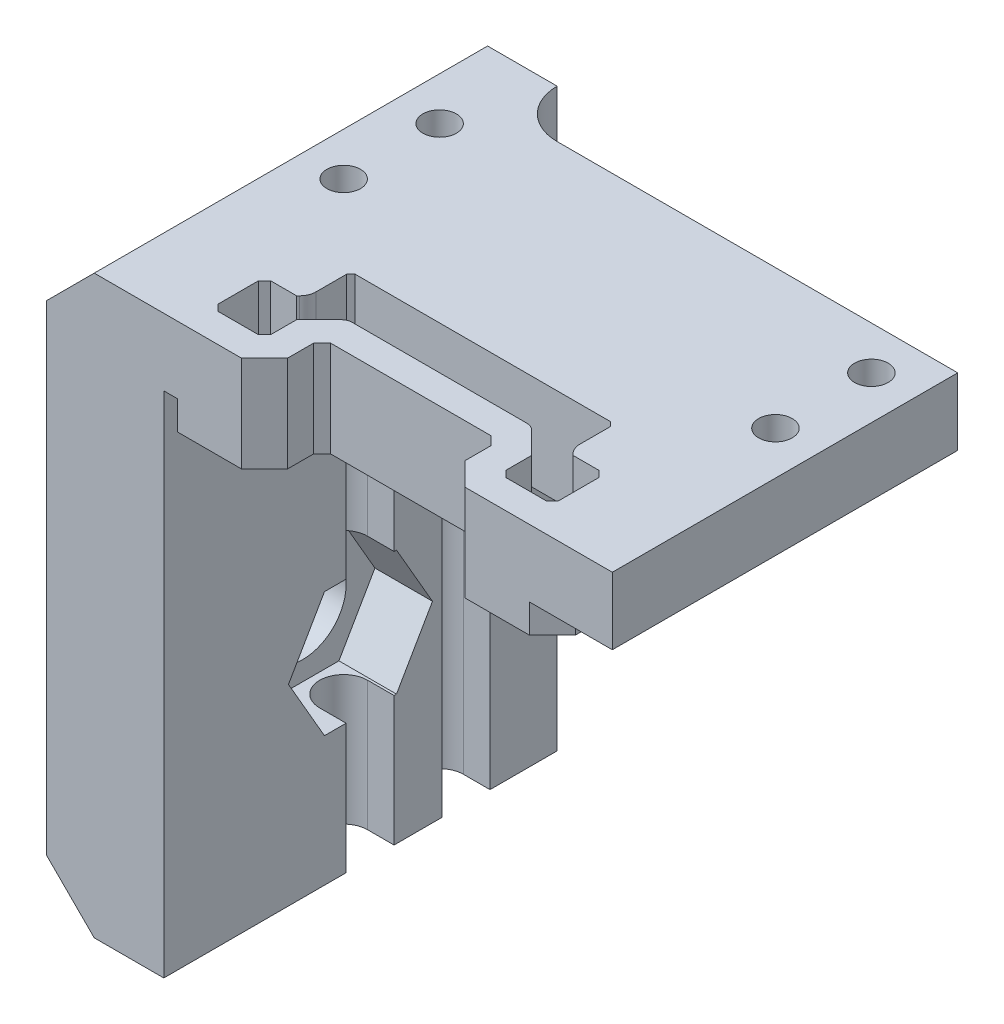
SolidWorks part; units mm, degrees
ref_plane "Front Plane" through (0, 0, 0) normal (0, 0, 1) x (1, 0, 0)
ref_plane "Top Plane" through (0, 0, 0) normal (0, 1, 0) x (1, 0, 0)
ref_plane "Right Plane" through (0, 0, 0) normal (1, 0, 0) x (0, 0, -1)
ref_plane "Plane1" through (0, 200, 0) normal (0, 1, 0) x (1, 0, 0)
sketch "Sketch1" plane through (0, 200, 0) normal (0, 1, 0) x (1, 0, 0)
  line L0 (0, -3.8557) -> (0.25, -4)
  line L1 (0.25, -4) -> (9.0787, -4)
  line L2 (10.1394, -4.4394) -> (12.5, -6.8)
  line L3 (12.5, -6.8) -> (12.5, -9.5)
  line L4 (12.5, -9.5) -> (13, -10)
  line L5 (13, -10) -> (17, -10)
  line L6 (17, -10) -> (17.5, -9.5)
  line L7 (17.5, -9.5) -> (17.5, -5.5)
  line L8 (17.5, -5.5) -> (17, -5)
  line L9 (17, -5) -> (14.3, -5)
  line L10 (14.3, -5) -> (14.0858, -4.7858)
  line L11 (13.5, -3.3716) -> (13.5, -0.3)
  line L12 (13.5, -0.3) -> (13.2, 0)
  line L13 (13.2, 0) -> (7.5, 0)
  line L14 (7.5, 0) -> (7.4, -0.1)
  line L15 (7.4, -0.1) -> (-7.4, -0.1)
  line L16 (-7.4, -0.1) -> (-7.5, 0)
  line L17 (-7.5, 0) -> (-13.2, 0)
  line L18 (-13.2, 0) -> (-13.5, -0.3)
  line L19 (-13.5, -0.3) -> (-13.5, -3.3716)
  line L20 (-14.0858, -4.7858) -> (-14.3, -5)
  line L21 (-14.3, -5) -> (-17, -5)
  line L22 (-17, -5) -> (-17.5, -5.5)
  line L23 (-17.5, -5.5) -> (-17.5, -9.5)
  line L24 (-17.5, -9.5) -> (-17, -10)
  line L25 (-17, -10) -> (-13, -10)
  line L26 (-13, -10) -> (-12.5, -9.5)
  line L27 (-12.5, -9.5) -> (-12.5, -6.8)
  line L28 (-12.5, -6.8) -> (-10.1394, -4.4394)
  line L29 (-9.0787, -4) -> (-0.25, -4)
  line L30 (-0.25, -4) -> (0, -3.8557)
  arc A0 (9.0787, -4) -> (10.1394, -4.4394) centre (9.0787, -5.5) cw
  arc A1 (14.0858, -4.7858) -> (13.5, -3.3716) centre (15.5, -3.3716) cw
  arc A2 (-13.5, -3.3716) -> (-14.0858, -4.7858) centre (-15.5, -3.3716) cw
  arc A3 (-10.1394, -4.4394) -> (-9.0787, -4) centre (-9.0787, -5.5) cw
extrude "Boss-Extrude1" add sketch "Sketch1" against normal blind 400
ref_plane "Plane2" through (0, 210, 0) normal (0, 1, 0) x (1, 0, 0)
sketch "Sketch2" plane through (0, 210, 0) normal (0, 1, 0) x (1, 0, 0)
  line L0 (-8.3538, -7.25) -> (8.3538, -7.25)
  line L1 (8.3538, -7.25) -> (9.25, -8.1462)
  line L2 (13.3036, 0.25) -> (-13.3036, 0.25)
  line L3 (-13.3036, 0.25) -> (-13.75, -0.1965)
  line L4 (-13.75, -0.1965) -> (-13.75, -3.3716)
  line L5 (-14.2626, -4.609) -> (-14.4036, -4.75)
  line L6 (-14.4036, -4.75) -> (-17.1036, -4.75)
  line L7 (-17.1036, -4.75) -> (-17.75, -5.3965)
  line L8 (-17.75, -5.3965) -> (-17.75, -9.6036)
  line L9 (-17.75, -9.6036) -> (-17.1036, -10.25)
  line L10 (-17.1036, -10.25) -> (-12.8965, -10.25)
  line L11 (-12.8965, -10.25) -> (-12.25, -9.6036)
  line L12 (-12.25, -9.6036) -> (-12.25, -6.9036)
  line L13 (-12.25, -6.9036) -> (-9.9626, -4.6162)
  line L14 (-9.0787, -4.25) -> (9.0787, -4.25)
  line L15 (9.9626, -4.6162) -> (12.25, -6.9036)
  line L16 (12.25, -6.9036) -> (12.25, -9.6036)
  line L17 (12.25, -9.6036) -> (12.8965, -10.25)
  line L18 (12.8965, -10.25) -> (17.1036, -10.25)
  line L19 (17.1036, -10.25) -> (17.75, -9.6036)
  line L20 (17.75, -9.6036) -> (17.75, -5.3965)
  line L21 (17.75, -5.3965) -> (17.1036, -4.75)
  line L22 (17.1036, -4.75) -> (14.4036, -4.75)
  line L23 (14.4036, -4.75) -> (14.2626, -4.609)
  line L24 (13.75, -3.3716) -> (13.75, -0.1965)
  line L25 (13.75, -0.1965) -> (13.3036, 0.25)
  line L26 (9.25, -8.1462) -> (9.25, -10.8462)
  line L27 (9.25, -10.8462) -> (11.6538, -13.25)
  line L28 (11.6538, -13.25) -> (18.3462, -13.25)
  line L29 (18.3462, -13.25) -> (20.75, -10.8462)
  line L30 (20.75, -10.8462) -> (20.75, -4.1538)
  line L31 (20.75, -4.1538) -> (18.3462, -1.75)
  line L32 (18.3462, -1.75) -> (16.75, -1.75)
  line L33 (16.75, -1.75) -> (16.75, -1.75)
  line L34 (16.75, -1.75) -> (16.75, 1.0462)
  line L35 (16.75, 1.0462) -> (14.5462, 3.25)
  line L36 (14.5462, 3.25) -> (-14.5462, 3.25)
  line L37 (-14.5462, 3.25) -> (-16.75, 1.0462)
  line L38 (-16.75, 1.0462) -> (-16.75, -1.75)
  line L39 (-16.75, -1.75) -> (-16.75, -1.75)
  line L40 (-16.75, -1.75) -> (-18.3462, -1.75)
  line L41 (-18.3462, -1.75) -> (-20.75, -4.1538)
  line L42 (-20.75, -4.1538) -> (-20.75, -10.8462)
  line L43 (-20.75, -10.8462) -> (-18.3462, -13.25)
  line L44 (-18.3462, -13.25) -> (-11.6538, -13.25)
  line L45 (-11.6538, -13.25) -> (-9.25, -10.8462)
  line L46 (-9.25, -10.8462) -> (-9.25, -8.1462)
  line L47 (-9.25, -8.1462) -> (-8.3538, -7.25)
  arc A0 (-14.2626, -4.609) -> (-13.75, -3.3716) centre (-15.5, -3.3716) ccw
  arc A1 (-9.0787, -4.25) -> (-9.9626, -4.6162) centre (-9.0787, -5.5) ccw
  arc A2 (9.9626, -4.6162) -> (9.0787, -4.25) centre (9.0787, -5.5) ccw
  arc A3 (13.75, -3.3716) -> (14.2626, -4.609) centre (15.5, -3.3716) ccw
  arc A4 (8.3538, -7.25) -> (8.3538, -7.25) centre (8.3538, -7.25) ccw
  arc A5 (16.75, -1.75) -> (16.75, -1.75) centre (16.75, -1.75) ccw
  arc A6 (-16.75, -1.75) -> (-16.75, -1.75) centre (-16.75, -1.75) ccw
  arc A7 (-8.3538, -7.25) -> (-8.3538, -7.25) centre (-8.3538, -7.25) ccw
  dimension "D1" = 3
extrude "Boss-Extrude2" add sketch "Sketch2" along normal blind 10 separate body
sketch "Sketch3" plane through (0, 200, 0) normal (0, 1, 0) x (1, 0, 0)
  line L0 (7.4, -0.1) -> (-7.4, -0.1) construction
  circle A0 centre (0, -0.1) radius 43.001
extrude "Cut-Extrude1" cut sketch "Sketch3" against normal blind 447.3602
sketch "Sketch4" plane through (0, 210, 0) normal (0, -1, 0) x (-1, 0, 0)
  line L0 (-13.3036, 0.25) -> (13.3036, 0.25) construction
  line L1 (27, 22.75) -> (-27, 22.75)
  line L2 (27, 22.75) -> (27, -13.25)
  line L3 (27, -13.25) -> (18.3462, -13.25)
  line L4 (-27, 22.75) -> (-27, -13.25)
  line L5 (-27, -13.25) -> (-18.3462, -13.25)
  line L25 (8.3538, -7.25) -> (9.25, -8.1462)
  line L26 (9.25, -8.1462) -> (9.25, -10.8462)
  line L27 (9.25, -10.8462) -> (11.6538, -13.25)
  line L28 (11.6538, -13.25) -> (18.3462, -13.25)
  line L29 (18.3462, -13.25) -> (20.75, -10.8462)
  line L30 (20.75, -10.8462) -> (20.75, -4.1538)
  line L31 (20.75, -4.1538) -> (18.3462, -1.75)
  line L32 (18.3462, -1.75) -> (16.75, -1.75)
  line L33 (16.75, -1.75) -> (16.75, 1.0462)
  line L34 (16.75, 1.0462) -> (14.5462, 3.25)
  line L35 (14.5462, 3.25) -> (-14.5462, 3.25)
  line L36 (-14.5462, 3.25) -> (-16.75, 1.0462)
  line L37 (-16.75, 1.0462) -> (-16.75, -1.75)
  line L38 (-16.75, -1.75) -> (-18.3462, -1.75)
  line L39 (-18.3462, -1.75) -> (-20.75, -4.1538)
  line L40 (-20.75, -4.1538) -> (-20.75, -10.8462)
  line L41 (-20.75, -10.8462) -> (-18.3462, -13.25)
  line L42 (-18.3462, -13.25) -> (-11.6538, -13.25)
  line L43 (-11.6538, -13.25) -> (-9.25, -10.8462)
  line L44 (-9.25, -10.8462) -> (-9.25, -8.1462)
  line L45 (-9.25, -8.1462) -> (-8.3538, -7.25)
  line L46 (-8.3538, -7.25) -> (8.3538, -7.25)
  line L47 (8.3538, -7.25) -> (9.25, -8.1462)
  line L48 (9.25, -8.1462) -> (9.25, -10.8462)
  line L49 (9.25, -10.8462) -> (11.6538, -13.25)
  line L50 (11.6538, -13.25) -> (18.3462, -13.25)
  line L51 (18.3462, -13.25) -> (20.75, -10.8462)
  line L52 (20.75, -10.8462) -> (20.75, -4.1538)
  line L53 (20.75, -4.1538) -> (18.3462, -1.75)
  line L54 (18.3462, -1.75) -> (16.75, -1.75)
  line L55 (16.75, -1.75) -> (16.75, 1.0462)
  line L56 (16.75, 1.0462) -> (14.5462, 3.25)
  line L57 (14.5462, 3.25) -> (-14.5462, 3.25)
  line L58 (-14.5462, 3.25) -> (-16.75, 1.0462)
  line L59 (-16.75, 1.0462) -> (-16.75, -1.75)
  line L60 (-16.75, -1.75) -> (-18.3462, -1.75)
  line L61 (-18.3462, -1.75) -> (-20.75, -4.1538)
  line L62 (-20.75, -4.1538) -> (-20.75, -10.8462)
  line L63 (-20.75, -10.8462) -> (-18.3462, -13.25)
  line L64 (-18.3462, -13.25) -> (-11.6538, -13.25)
  line L65 (-11.6538, -13.25) -> (-9.25, -10.8462)
  line L66 (-9.25, -10.8462) -> (-9.25, -8.1462)
  line L67 (-9.25, -8.1462) -> (-8.3538, -7.25)
  line L68 (-8.3538, -7.25) -> (8.3538, -7.25)
  point P8 (0, 22.75)
  point P29 (0, 0.25)
  line M32 (20.75, -4.1538) -> (18.3462, -1.75)
  line M33 (18.3462, -1.75) -> (16.75, -1.75)
  line M34 (16.75, -1.75) -> (16.75, 1.0462)
  line M35 (16.75, 1.0462) -> (14.5462, 3.25)
  line M36 (14.5462, 3.25) -> (-14.5462, 3.25)
  line M37 (-14.5462, 3.25) -> (-16.75, 1.0462)
  line M38 (-16.75, 1.0462) -> (-16.75, -1.75)
  line M39 (-16.75, -1.75) -> (-18.3462, -1.75)
  line M40 (-18.3462, -1.75) -> (-20.75, -4.1538)
  dimension "D2" = 19.5
  dimension "D3" = 54
  dimension "D4" = 0
  dimension "D1" = 0
extrude "Boss-Extrude3" add sketch "Sketch4" against normal blind 7 contours L1 M40 M39 M38 M37 M36 M35 M34 M33 M32 region at (0, 210, -9.587)
sketch "Sketch5" plane through (0, 210, 0) normal (0, -1, 0) x (-1, 0, 0)
  line L0 (0, 22.75) -> (0, 9.6848) construction
  line L1 (27, 22.75) -> (-27, 22.75) construction
  line L2 (27, 22.75) -> (27, -13.25) construction
  circle A0 centre (22.5, 18.25) radius 1.75
  circle A1 centre (22.5, 8.25) radius 1.75
  circle A2 centre (-22.5, 8.25) radius 1.75
  circle A3 centre (-22.5, 18.25) radius 1.75
  dimension "D4" = 3.5
  dimension "D1" = 10
  dimension "D2" = 4.5
  dimension "D3" = 4.5
extrude "Cut-Extrude2" cut sketch "Sketch5" against normal blind 33
sketch "Sketch6" plane through (-27, 0, 0) normal (-1, 0, 0) x (0, 0, 1)
  line L1 (-22.75, 210) -> (13.25, 210)
  line L2 (-22.75, 210) -> (-22.75, 270)
  line L3 (-22.75, 270) -> (13.25, 270)
  line L4 (13.25, 210) -> (13.25, 270)
  dimension "D1" = 60
extrude "Boss-Extrude4" add sketch "Sketch6" along normal blind 5
sketch "Sketch7" plane through (0, 217, 0) normal (0, 1, 0) x (1, 0, 0)
  line L0 (-20.75, -10.8462) -> (-20.75, -4.1538) construction
  line L1 (-27, -13.25) -> (-19.75, -13.25)
  line L2 (-27, -13.25) -> (-27, 2.75)
  line L3 (-27, 2.75) -> (-19.75, 2.75)
  line L4 (-19.75, -13.25) -> (-19.75, 2.75)
  dimension "D1" = 1
  dimension "D2" = 16
extrude "Boss-Extrude5" add sketch "Sketch7" along normal up to surface (53 mm away) up to face at (-29.5, 270, -4.75)
sketch "Sketch8" plane through (0, 0, -22.75) normal (0, 0, -1) x (-1, 0, 0)
  line L0 (32, 210) -> (-27, 210) construction
  line L1 (32, 270) -> (19.75, 270)
  line L2 (32, 270) -> (32, 210)
  line L3 (32, 210) -> (19.75, 210)
  line L4 (19.75, 270) -> (19.75, 210)
  dimension "D1" = 0
extrude "Boss-Extrude6" add sketch "Sketch8" along normal blind 5
fillet "Fillet1" radius 5 1 edges at (-19.75, 213.5, -22.75)
sketch "Sketch10" plane through (-27, 0, 0) normal (1, 0, 0) x (0, 0, -1)
  line L0 (22.75, 270) -> (22.75, 217) construction
  line L1 (2.75, 270) -> (22.75, 270)
  line L2 (2.75, 270) -> (2.75, 230)
  line L3 (2.75, 230) -> (22.75, 230)
  line L4 (22.75, 270) -> (22.75, 230)
  dimension "D1" = 40
extrude "Boss-Extrude7" add sketch "Sketch10" along normal up to surface (7.25 mm away) up to face at (-19.75, 231, 6.375)
sketch "Sketch9" plane through (-19.75, 0, 0) normal (1, 0, 0) x (0, 0, -1)
  line L0 (-13.25, 250) -> (27.75, 250) construction
  line L1 (14.7555, 250) -> (11.0027, 256.5)
  line L2 (11.0027, 256.5) -> (3.4972, 256.5)
  line L3 (3.4972, 256.5) -> (-0.2556, 250)
  line L4 (-0.2556, 250) -> (3.4972, 243.5)
  line L5 (3.4972, 243.5) -> (11.0027, 243.5)
  line L6 (11.0027, 243.5) -> (14.7555, 250)
  line L8 (-13.25, 270) -> (-13.25, 217) construction
  line L9 (27.75, 270) -> (27.75, 217) construction
  line L10 (27.75, 270) -> (-13.25, 270) construction
  circle A0 centre (7.25, 250) radius 6.5 construction
  point P16 (7.25, 250)
  dimension "D1" = 13
  dimension "D2" = 20
extrude "Cut-Extrude3" cut sketch "Sketch9" against normal blind 6
sketch "Sketch11" plane through (0, 217, 0) normal (0, 1, 0) x (1, 0, 0)
  line L0 (-22.5, 20.75) -> (-17.8248, 20.75)
  line L1 (-17.8248, 20.75) -> (-17.8248, 15.75)
  line L2 (-17.8248, 15.75) -> (-22.5, 15.75)
  line L3 (-22.5, 10.75) -> (-17.8248, 10.75)
  line L4 (-17.8248, 10.75) -> (-17.8248, 5.75)
  line L5 (-17.8248, 5.75) -> (-22.5, 5.75)
  arc A0 (-22.5, 20.75) -> (-22.5, 15.75) centre (-22.5, 18.25) ccw
  arc A1 (-22.5, 10.75) -> (-22.5, 5.75) centre (-22.5, 8.25) ccw
  dimension "D1" = 5
  dimension "D2" = 5
extrude "Cut-Extrude4" cut sketch "Sketch11" along normal through all
sketch "Sketch12" plane through (-25.75, 0, 0) normal (1, 0, 0) x (0, 0, -1)
  line L0 (14.7555, 250) -> (-0.2556, 250) construction
  circle A0 centre (7.25, 250) radius 4.5
  dimension "D1" = 9
extrude "Cut-Extrude5" cut sketch "Sketch12" against normal blind 16
chamfer "Chamfer2" distance 5 angle 45 1 edges at (-32, 270, -7.25)
chamfer "Chamfer3" distance 5 angle 45 1 edges at (-32, 210, -7.25)
sketch "Sketch13" plane through (-32, 0, 0) normal (-1, 0, 0) x (0, 0, 1)
  circle A0 centre (-7.25, 250) radius 4.5
  circle A1 centre (-7.25, 250) radius 6.5
  dimension "D1" = 2
extrude "Boss-Extrude8" add sketch "Sketch13" along normal blind 1
fillet "Fillet2" radius 1 1 edges at (-32, 250, -13.75)
mirror "Mirror1" about plane through (0, 210, 0) normal (0, -1, 0) of bodies 115
sketch "Sketch14" plane through (0, 210, 0) normal (0, 1, 0) x (1, 0, 0)
  circle A0 centre (0, 0) radius 56.9714
extrude "Cut-Extrude6" cut sketch "Sketch14" along normal blind 95
